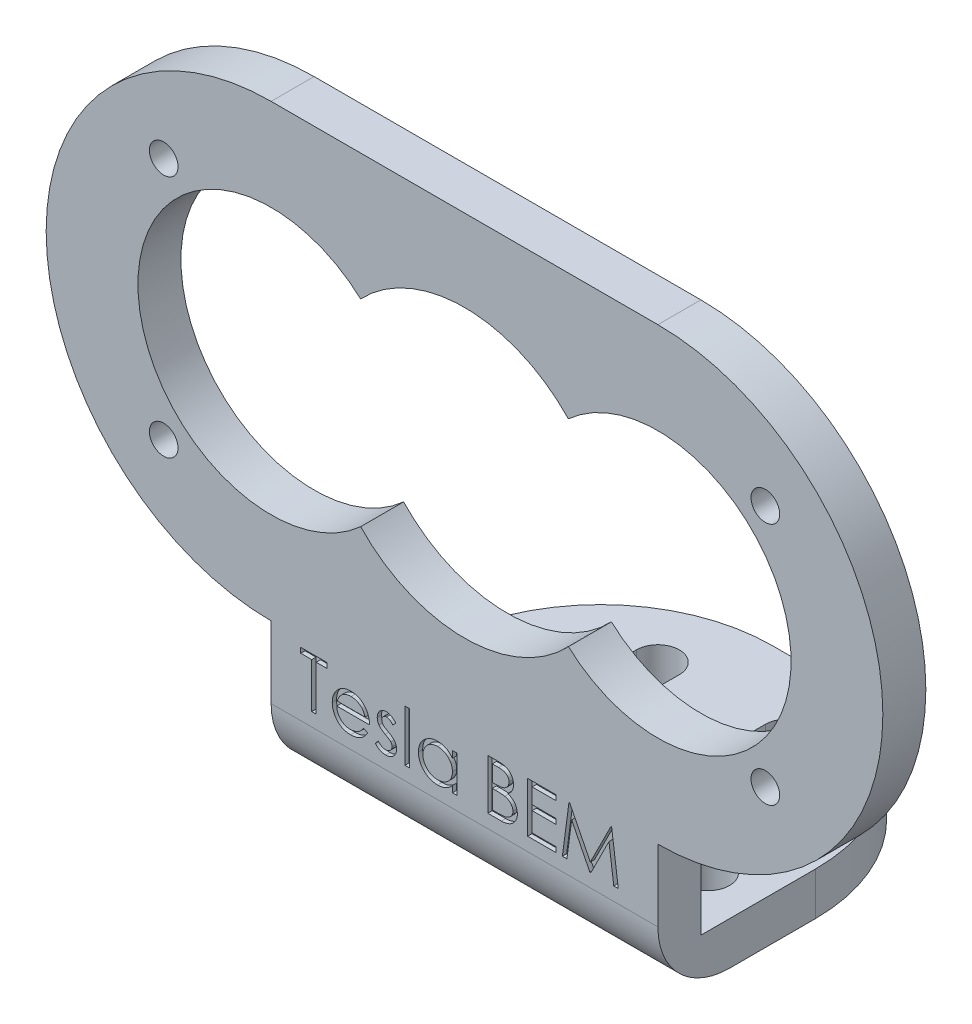
SolidWorks part; units mm, degrees
ref_plane "Alzado" through (0, 0, 0) normal (0, 0, 1) x (1, 0, 0)
ref_plane "Planta" through (0, 0, 0) normal (0, 1, 0) x (1, 0, 0)
ref_plane "Vista lateral" through (0, 0, 0) normal (1, 0, 0) x (0, 0, -1)
sketch "Croquis1" plane through (0, 0, 0) normal (0, 0, 1) x (1, 0, 0)
  line L0 (13.5, 10) -> (13.5, -10) construction
  line L3 (0, -15.7043) -> (0, -25.7043)
  line L4 (0, -25.7043) -> (27, -25.7043)
  line L5 (-9.2975, 0) -> (36.2975, 0) construction
  line L6 (0, 15.7043) -> (27, 15.7043)
  line L8 (27, -15.7043) -> (27, -25.7043)
  arc A0 (6.2479, 6.8853) -> (6.2479, -6.8853) centre (0, 0) ccw
  arc A1 (20.7521, 6.8853) -> (20.7521, -6.8853) centre (27, 0) cw
  arc A2 (6.2479, -6.8853) -> (20.7521, -6.8853) centre (13.5, 0) ccw
  arc A3 (20.7521, 6.8853) -> (6.2479, 6.8853) centre (13.5, 0) ccw
  circle A4 centre (-7.5, 8.5) radius 1
  circle A5 centre (34.5, 8.5) radius 1
  circle A6 centre (34.5, -8.5) radius 1
  circle A7 centre (-7.5, -8.5) radius 1
  arc A8 (0, 15.7043) -> (0, -15.7043) centre (0, 0) ccw
  arc A9 (27, 15.7043) -> (27, -15.7043) centre (27, 0) cw
  dimension "D1" = 9.2975
  dimension "D2" = 10
  dimension "D8" = 2
  dimension "D9" = 17.2043
  dimension "D10" = 17
  dimension "D11" = 42
  dimension "D3" = 14.5041
  dimension "D4" = 10
  dimension "D5" = 21
  dimension "D6" = 21
  dimension "D7" = 17
extrude "Saliente-Extruir1" add sketch "Croquis1" along normal blind 3
sketch "Croquis2" plane through (0, 0, 0) normal (0, 0, -1) x (-1, 0, 0)
  line L0 (0, -15.7043) -> (0, -25.7043) construction
  line L1 (-27, -25.7043) -> (0, -25.7043)
  line L2 (-27, -25.7043) -> (-27, -22.7043)
  line L3 (-27, -22.7043) -> (0, -22.7043)
  line L4 (0, -25.7043) -> (0, -22.7043)
  dimension "D1" = 3
extrude "Saliente-Extruir2" add sketch "Croquis2" along normal blind 20
fillet "Redondeo1" radius 12 2 edges at (0, -24.2043, -20) (27, -24.2043, -20)
sketch "Croquis3" plane through (0, -22.7043, 0) normal (0, 1, 0) x (1, 0, 0)
  line L0 (13.5, 0) -> (13.5, 20) construction
  line L1 (27, 0) -> (0, 0) construction
  line L2 (12, 20) -> (15, 20) construction
  line L3 (0, 0) -> (27, 0) construction
  line L4 (16.5, 15) -> (16.5, 3)
  line L5 (7.5, 15) -> (7.5, 3)
  line L6 (19.5, 15) -> (19.5, 3)
  line L7 (10.5, 15) -> (10.5, 3)
  arc A0 (7.5, 3) -> (10.5, 3) centre (9, 3) ccw
  arc A1 (7.5, 15) -> (10.5, 15) centre (9, 15) cw
  arc A2 (19.5, 3) -> (16.5, 3) centre (18, 3) cw
  arc A3 (19.5, 15) -> (16.5, 15) centre (18, 15) ccw
  circle A4 centre (3.5, 9) radius 1.5
  circle A5 centre (3.5, 4) radius 1.5
  circle A6 centre (23.5, 4) radius 1.5
  circle A7 centre (23.5, 9) radius 1.5
  dimension "D1" = 1.5
  dimension "D3" = 3
  dimension "D5" = 3
  dimension "D6" = 5
  dimension "D7" = 4
  dimension "D8" = 4
  dimension "D9" = 4
  dimension "D2" = 12
  dimension "D4" = 3
extrude "Cortar-Extruir1" cut sketch "Croquis3" against normal blind 20
sketch "Croquis4" plane through (0, 0, 3) normal (0, 0, 1) x (1, 0, 0)
  text T0 "Tesla BEM"
extrude "Cortar-Extruir2" cut sketch "Croquis4" against normal blind 0.3
fillet "Redondeo2" radius 5 1 edges at (13.5, -25.7043, 3)
